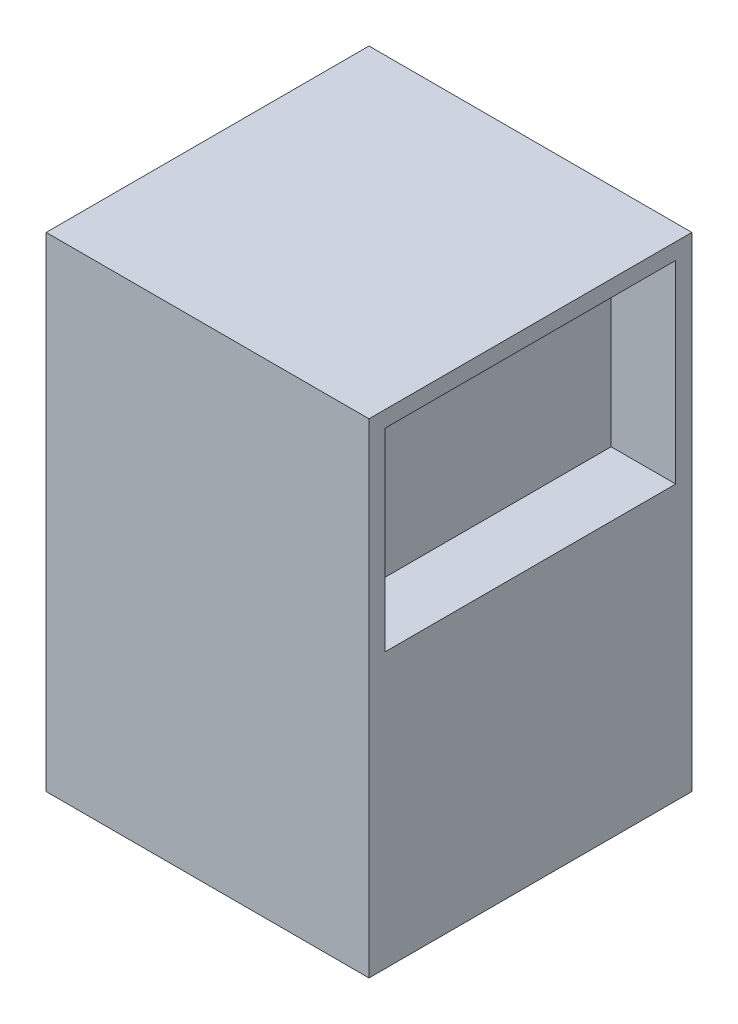
SolidWorks part; units mm, degrees
ref_plane "Front Plane" through (0, 0, 0) normal (0, 0, 1) x (1, 0, 0)
ref_plane "Top Plane" through (0, 0, 0) normal (0, 1, 0) x (1, 0, 0)
ref_plane "Right Plane" through (0, 0, 0) normal (1, 0, 0) x (0, 0, -1)
sketch "Sketch1" plane through (0, 0, 0) normal (0, 0, 1) x (1, 0, 0)
  line L0 (0, -995.1722) -> (0, 49004.8278) construction
  line L1 (-5, 8.8221) -> (5, 8.8221)
  line L2 (-5, 8.8221) -> (-5, -6.1779)
  line L3 (-5, -6.1779) -> (5, -6.1779)
  line L4 (5, 8.8221) -> (5, -6.1779)
  line L5 (0, -55) -> (0, 55) construction
  dimension "D1" = 15
  dimension "D2" = 10
  dimension "D3" = 5
  dimension "D4" = 0
extrude "Boss-Extrude1" add sketch "Sketch1" along normal blind 5 and the other way blind 5
sketch "Sketch3" plane through (5, 0, 0) normal (1, 0, 0) x (0, 0, -1)
  line L0 (5, 8.8221) -> (-5, 8.8221) construction
  line L1 (-4.5, 8.3221) -> (4.5, 8.3221)
  line L2 (-4.5, 8.3221) -> (-4.5, 2.3221)
  line L3 (-4.5, 2.3221) -> (4.5, 2.3221)
  line L4 (4.5, 8.3221) -> (4.5, 2.3221)
  line L5 (-5, -6.1779) -> (-5, 8.8221) construction
  line L6 (5, -6.1779) -> (5, 8.8221) construction
  dimension "D1" = 0.5
  dimension "D2" = 0.5
  dimension "D3" = 0.5
  dimension "D4" = 6
extrude "Cut-Extrude2" cut sketch "Sketch3" against normal blind 2
sketch "Sketch5" plane through (0, 0, -5) normal (0, 0, -1) x (-1, 0, 0)
  line L0 (-5, 8.8221) -> (5, 8.8221) construction
  line L1 (-4.2997, 8.8221) -> (4.2778, 8.8221)
  line L2 (-4.2997, 8.8221) -> (-4.2997, 6.9421)
  line L3 (-4.2997, 6.9421) -> (4.2778, 6.9421)
  line L4 (4.2778, 8.8221) -> (4.2778, 6.9421)
  dimension "D1" = 1.88
